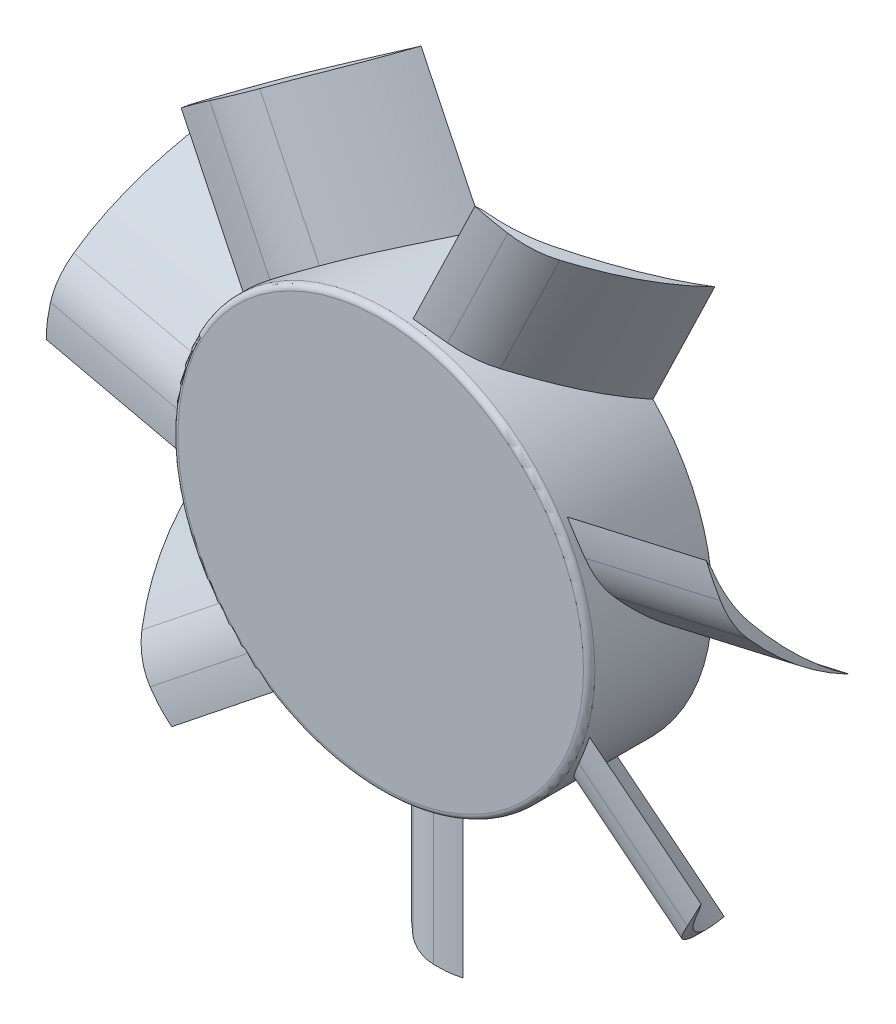
SolidWorks part; units mm, degrees
material "ПК/АБС"
ref_plane "Front" through (0, 0, 0) normal (0, 0, 1) x (1, 0, 0)
ref_plane "Top" through (0, 0, 0) normal (0, 1, 0) x (1, 0, 0)
ref_plane "Right" through (0, 0, 0) normal (1, 0, 0) x (0, 0, -1)
sketch "Эскиз1" plane through (0, 0, 0) normal (0, 0, 1) x (1, 0, 0)
  circle A0 centre (0, 0) radius 11
  dimension "D1" = 22
extrude "Бобышка-Вытянуть1" add sketch "Эскиз1" along normal blind 6.5
sketch "Эскиз2" plane through (0, 0, 0) normal (0, 0, -1) x (-1, 0, 0)
  circle A0 centre (0, 0) radius 9.75
  dimension "D1" = 19.5
extrude "Вырез-Вытянуть1" cut sketch "Эскиз2" against normal blind 5.5
sketch "Эскиз3" plane through (0, 0, 5.5) normal (0, 0, -1) x (-1, 0, 0)
  circle A0 centre (0, 0) radius 0.7
  dimension "D1" = 1.4
extrude "Бобышка-Вытянуть2" add sketch "Эскиз3" along normal blind 7.5
chamfer "Фаска1" distance 0.6 angle 45 1 edges at (-0.7, 0, -2)
sketch "Эскиз4" plane through (0, 0, 0) normal (0, 1, 0) x (1, 0, 0)
  line L0 (0, -6.5) -> (0, 0) construction
  line L1 (-11, -6.5) -> (11, -6.5) construction
  line L2 (0, 0) -> (11, -3.25) construction
  line L3 (11, -6.5) -> (11, 0) construction
  line L4 (11, -3.25) -> (-11, -3.25) construction
  line L5 (-11, 0) -> (-11, -6.5) construction
  line L7 (-3.75, -6.5) -> (3.75, -6.5) construction
  line L8 (-3.75, -6.5) -> (-3.75, 0) construction
  line L9 (-3.75, 0) -> (3.75, 0) construction
  line L10 (3.75, -6.5) -> (3.75, 0) construction
  line L11 (0, 0) -> (0, -6.5) construction
  line L12 (-3.75, -3.25) -> (3.75, -3.25) construction
  arc A2 (3.75, -5.9) -> (2.0764, -5.7876) centre (3.6109, 4.5482) cw
  arc A3 (0.0829, -4.887) -> (-3.75, 0) centre (9.9559, 6.8032) cw
  arc A4 (2.0764, -5.7876) -> (0.0829, -4.887) centre (2.6638, -1.831) cw
  arc A5 (3.75, -5.9) -> (3.4013, -5.7876) centre (6.34, 2.735) cw
  arc A6 (3.4013, -5.7876) -> (0.7393, -4.7108) centre (4.179, -0.0363) cw
  arc A7 (0.7393, -4.7108) -> (-3.75, 0) centre (11.8094, 10.3333) cw
  point P5 (0, -3.25)
  dimension "D3" = 0.6
  dimension "D4" = 4
  dimension "D1" = 6.5
  dimension "D2" = 7.5
extrude "Бобышка-Вытянуть3" add sketch "Эскиз4" against normal blind 23 from offset 10 offset against normal yes
pattern_circular "Круговой массив1" count 7 over 360 about axis through (0, 0, 6.5) along (0, 0, -1) of "Бобышка-Вытянуть3"
fillet "Скругление1" radius 0.3 1 edges at (11, 0, 6.5)
sketch "Эскиз5" plane through (0, 0, 6.5) normal (0, 0, 1) x (1, 0, 0)
  circle A0 centre (0, 0) radius 18.25
  dimension "D1" = 36.5
extrude "Вырез-Вытянуть2" cut sketch "Эскиз5" against normal blind 23 flip side to cut
